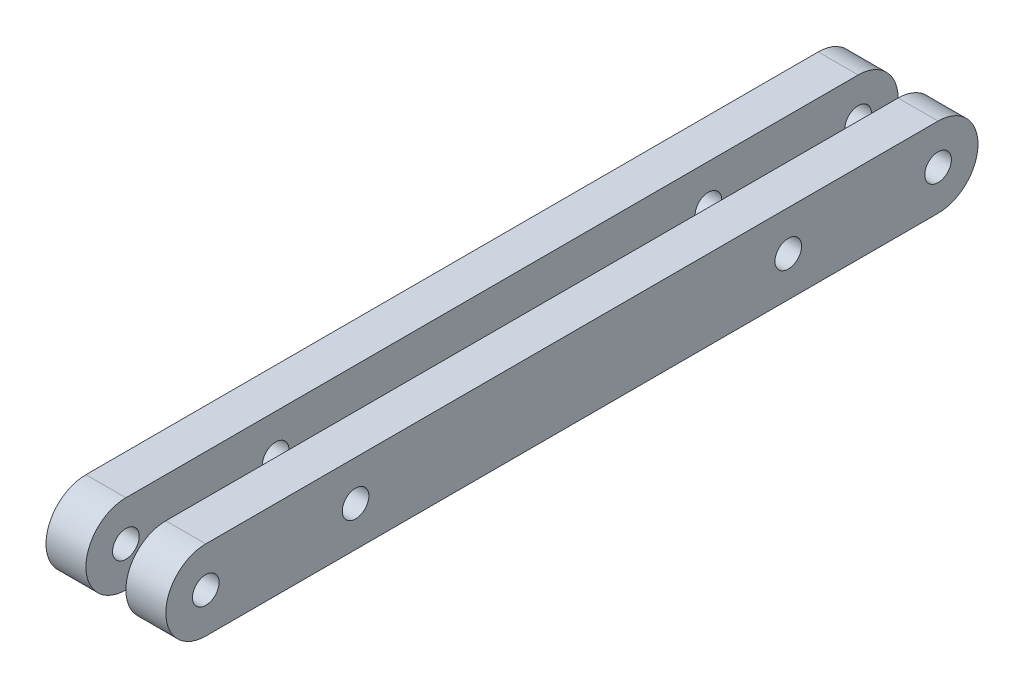
SolidWorks part; units mm, degrees
note: '?' marks a value the reader was unsure of.
ref_plane "Front Plane" through (0, 0, 0) normal (0, 0, 1) x (1, 0, 0)
ref_plane "Top Plane" through (0, 0, 0) normal (0, 1, 0) x (1, 0, 0)
ref_plane "Right Plane" through (0, 0, 0) normal (1, 0, 0) x (0, 0, -1)
sketch "length (ref to equation file)" plane through (0, 0, 0) normal (1, 0, 0) x (0, 0, -1)
  line L0 (0, 0) -> (110, 0)
  dimension "D1" = 110
ref_axis "pivot w/ link 1" through (0, 0, 0) along (1, 0, 0)?
ref_axis "pivot w/ platform" through (0, 0, -110) along (1, 0, 0)?
ref_plane "Plane1" through (3, 0, 0) normal (1, 0, 0) x (0, 0, -1)
sketch "Sketch1" plane through (3, 0, 0) normal (1, 0, 0) x (0, 0, -1)
  line L0 (0, 0) -> (110, 0) construction
  line L1 (0, 6) -> (110, 6)
  line L2 (0, -6) -> (110, -6)
  arc A0 (0, 6) -> (0, -6) centre (0, 0) ccw
  arc A1 (110, -6) -> (110, 6) centre (110, 0) ccw
  point P4 (55, 0)
  dimension "D1" = 12
extrude "Boss-Extrude1" add sketch "Sketch1" along normal blind 6 contours L2 A1 L1 A0
sketch "Sketch2" plane through (9, 0, 0) normal (1, 0, 0) x (0, 0, -1)
  circle A0 centre (0, 0) radius 2
  circle A2 centre (110, 0) radius 2
  circle A5 centre (0, 0) radius 2 construction
extrude "Cut-Extrude1" cut sketch "Sketch2" against normal through all and the other way through all
mirror "Mirror4" about plane through (0, 0, 0) normal (1, 0, 0) of bodies 103
sketch "Sketch3" plane through (3, 0, 0) normal (1, 0, 0) x (0, 0, -1)
  line L0 (0, 0) -> (110, 0) construction
  line L1 (22.5, 0) -> (87.5, 0)
  line L2 (0, 6) -> (110, 6) construction
  line L3 (22.5, 6) -> (87.5, 6)
  line L4 (22.5, 6) -> (22.5, -6)
  line L5 (22.5, -6) -> (87.5, -6)
  line L6 (87.5, 6) -> (87.5, -6)
  line L7 (0, -6) -> (110, -6) construction
  point P5 (55, 0)
  point P7 (55, 0)
  dimension "D1" = 65
extrude "Boss-Extrude2" [suppressed] add sketch "Sketch3" against normal up to surface (6 mm away)
sketch "Sketch5" plane through (9, 0, 0) normal (1, 0, 0) x (0, 0, -1)
  point P0 (87.5, 0)
  point P2 (22.5, 0)
hole_wizard "Ø4.0mm Dowel Hole1" positions "Sketch5" profile "Sketch6" hole size "Ø4.0" standard "ANSI Metric" end condition through all
sketch "Sketch6" plane through (9, 0, -87.5) normal (0, 1, 0) x (0, 0, -1)
  line L0 (0, 0) -> (0, 18)
  line L1 (0, 18) -> (2, 18)
  line L2 (2, 18) -> (2, 0)
  line L5 (2, 0) -> (0, 0)
  line L11 (0, -6.35) -> (0, 107.95) construction
  dimension "Thru Hole Dia." = 4
  dimension "Thru Hole Depth" = 18
equation "\"link 2\"= 110mm"
equation "\"D1@length (ref to equation file)\" = \"link 2\""
equation "\"link 1 thickness\" = 6mm"
equation "\"beam width\"= 30mm"
equation "\"beam side wall thickness\"= 3mm"
equation "\"D1@Plane1\" = \"link 2 plane\""
equation "\"link 2 plane\"= \"link 1 thickness\" / 2"
equation "\"motor center z\" = 35mm"
equation "\"motor center y\" = 20mm"
equation "\"link 1\" = 40mm"
equation "\"pivot height\"= 140mm"
equation "\"beam length\" = 185mm"
equation "\"camera height\" = 250mm"
equation "\"link height\"= 12mm"
equation "\"D1@Sketch1\"=\"link height\""
equation "\"D1@Boss-Extrude1\"=\"link 1 thickness\""
